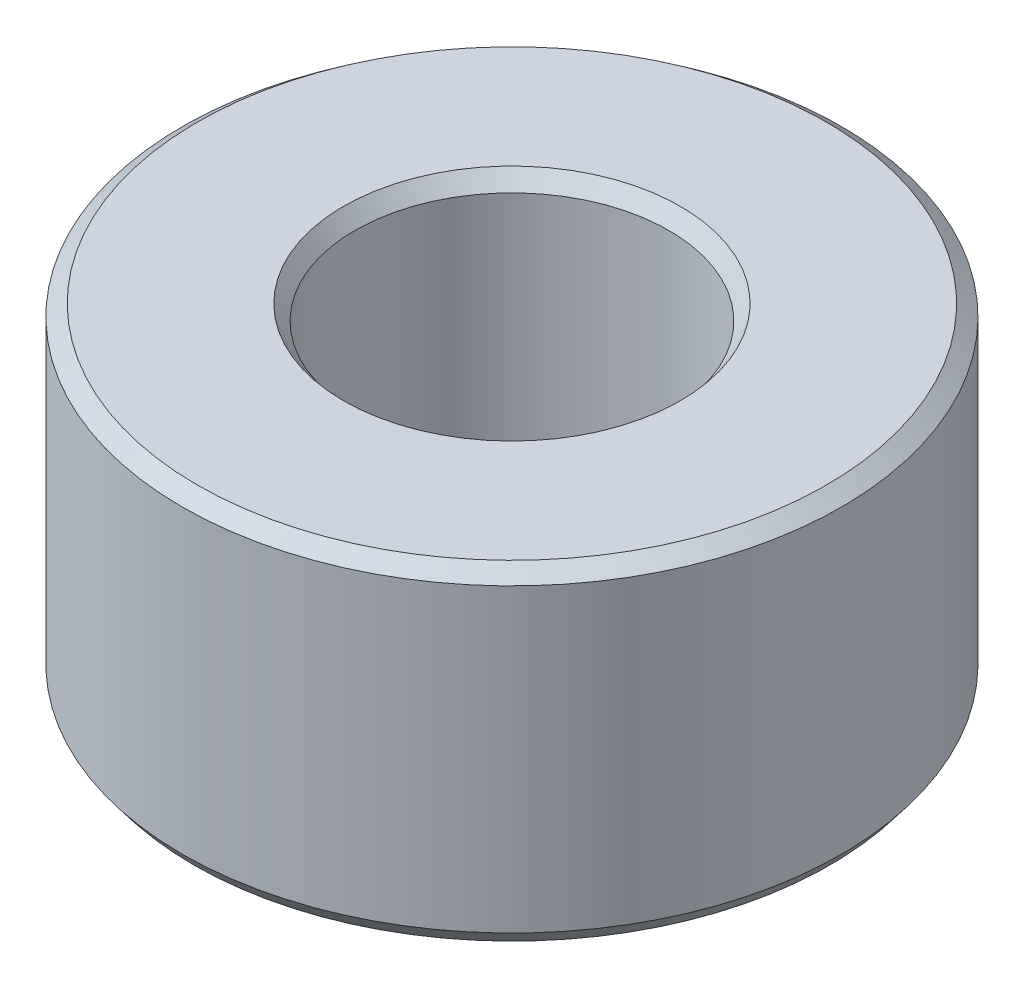
SolidWorks part; units mm, degrees
ref_plane "Front Plane" through (0, 0, 0) normal (0, 0, 1) x (1, 0, 0)
ref_plane "Top Plane" through (0, 0, 0) normal (0, 1, 0) x (1, 0, 0)
ref_plane "Right Plane" through (0, 0, 0) normal (1, 0, 0) x (0, 0, -1)
sketch "Sketch1" plane through (0, 0, 0) normal (0, 1, 0) x (1, 0, 0)
  circle A0 centre (0, 0) radius 57.5
  dimension "SLEEVE_OD" = 115
extrude "Boss-Extrude1" add sketch "Sketch1" along normal blind 57.0969
sketch "Sketch2" plane through (0, 0, 0) normal (0, 1, 0) x (1, 0, 0)
  circle A0 centre (0, 0) radius 27.3806
  dimension "BORE_D" = 54.7612
extrude "Cut-Extrude1" cut sketch "Sketch2" along normal through all
chamfer "Chamfer1" distance 2.004 angle 52.753 4 edges at (0, 57.0969, 27.3806) (0, 0, 27.3806) (0, 0, 57.5) (0, 57.0969, 57.5) first distance on face at (0, 57.0969, 27.3806) first distance on face at (0, 0, 27.3806) first distance on face at (0, 57.0969, 57.5)
